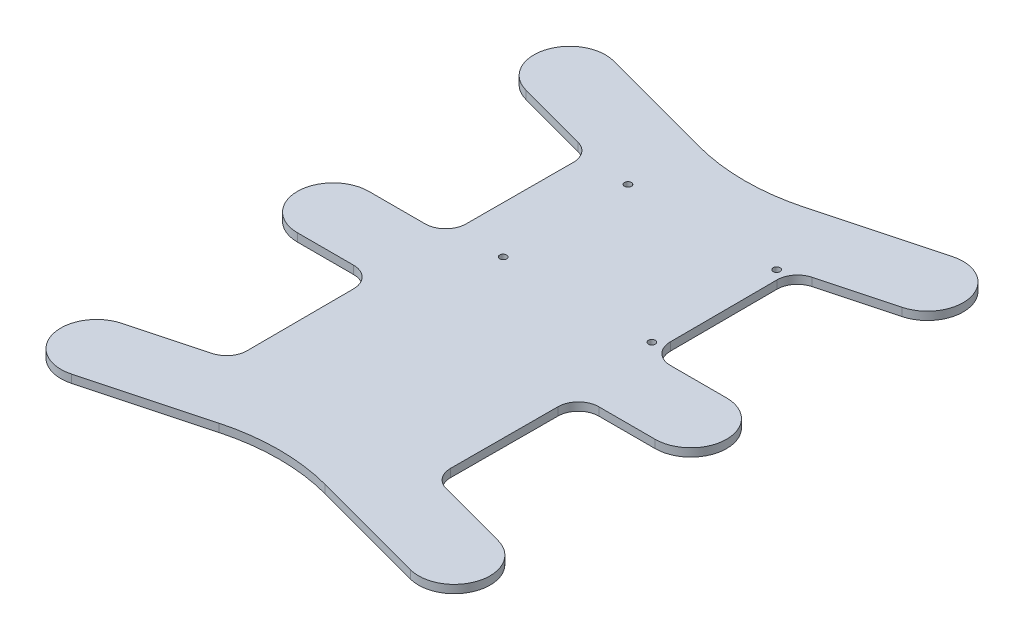
SolidWorks part; units mm, degrees
ref_plane "Front Plane" through (0, 0, 0) normal (0, 0, 1) x (1, 0, 0)
ref_plane "Top Plane" through (0, 0, 0) normal (0, 1, 0) x (1, 0, 0)
ref_plane "Right Plane" through (0, 0, 0) normal (1, 0, 0) x (0, 0, -1)
sketch "Sketch1" plane through (0, 0, 0) normal (0, 1, 0) x (1, 0, 0)
  line L0 (0, 32.1883) -> (0, -21.4181) construction
  line L1 (0, 0) -> (27.1703, 0) construction
  line L2 (-70, 14) -> (-40, 14)
  line L3 (-40, 14) -> (-39.8161, 70)
  line L4 (-39.8161, 70) -> (-73.6235, 79.0587)
  line L5 (-66.3765, 106.1046) -> (0, 88.3191)
  line L10 (-66.3765, 106.1046) -> (-73.6235, 79.0587) construction
  line L12 (-70, 14) -> (-70, -14) construction
  line L14 (-66.3765, -106.1046) -> (0, -88.3191)
  line L15 (-39.8161, -70) -> (-73.6235, -79.0587)
  line L16 (-40, -14) -> (-39.8161, -70)
  line L17 (-70, -14) -> (-40, -14)
  line L18 (66.3765, -106.1046) -> (0, -88.3191)
  line L19 (66.3765, 106.1046) -> (0, 88.3191)
  line L20 (70, 14) -> (70, -14) construction
  line L21 (66.3765, 106.1046) -> (73.6235, 79.0587) construction
  line L22 (70, -14) -> (40, -14)
  line L23 (40, -14) -> (39.8161, -70)
  line L24 (39.8161, -70) -> (73.6235, -79.0587)
  line L25 (39.8161, 70) -> (73.6235, 79.0587)
  line L26 (40, 14) -> (39.8161, 70)
  line L27 (70, 14) -> (40, 14)
  arc A0 (-70, 14) -> (-70, -14) centre (-70, 0) ccw
  arc A1 (-66.3765, 106.1046) -> (-73.6235, 79.0587) centre (-70, 92.5816) ccw
  arc A11 (-66.3765, -106.1046) -> (-73.6235, -79.0587) centre (-70, -92.5816) cw
  arc A18 (66.3765, -106.1046) -> (73.6235, -79.0587) centre (70, -92.5816) ccw
  arc A22 (66.3765, 106.1046) -> (73.6235, 79.0587) centre (70, 92.5816) cw
  arc A23 (70, 14) -> (70, -14) centre (70, 0) cw
  point P11 (0, 0)
  point P16 (0, 0)
  point P118 (-83.523, 96.2051)
  dimension "D2" = 14
  dimension "D3" = 70
  dimension "D1" = 75
  dimension "D5" = 30
  dimension "D6" = 35
  dimension "D7" = 56
extrude "Boss-Extrude1" add sketch "Sketch1" along normal blind 3.175
fillet "Fillet1" radius 80 2 edges at (0, 1.5875, -88.3191) (0, 1.5875, 88.3191)
fillet "Fillet2" radius 8 8 edges at (39.8161, 1.5875, 70) (40, 1.5875, 14) (40, 1.5875, -14) (39.8161, 1.5875, -70) (-39.8161, 1.5875, -70) (-40, 1.5875, -14) (-40, 1.5875, 14) (-39.8161, 1.5875, 70)
sketch "Sketch2" plane through (0, 3.175, 0) normal (0, 1, 0) x (1, 0, 0)
  circle A0 centre (36.3251, 67.2497) radius 1.35 construction
  circle A1 centre (36.486, 18.25) radius 1.35 construction
  circle A2 centre (-21.5137, 18.0595) radius 1.35 construction
  circle A3 centre (-21.6746, 67.0592) radius 1.35 construction
  circle A4 centre (36.3251, 67.2497) radius 1.35
  circle A5 centre (36.486, 18.25) radius 1.35
  circle A6 centre (-21.5137, 18.0595) radius 1.35
  circle A7 centre (-21.6746, 67.0592) radius 1.35
extrude "Cut-Extrude1" cut sketch "Sketch2" against normal through all both and the other way through all
